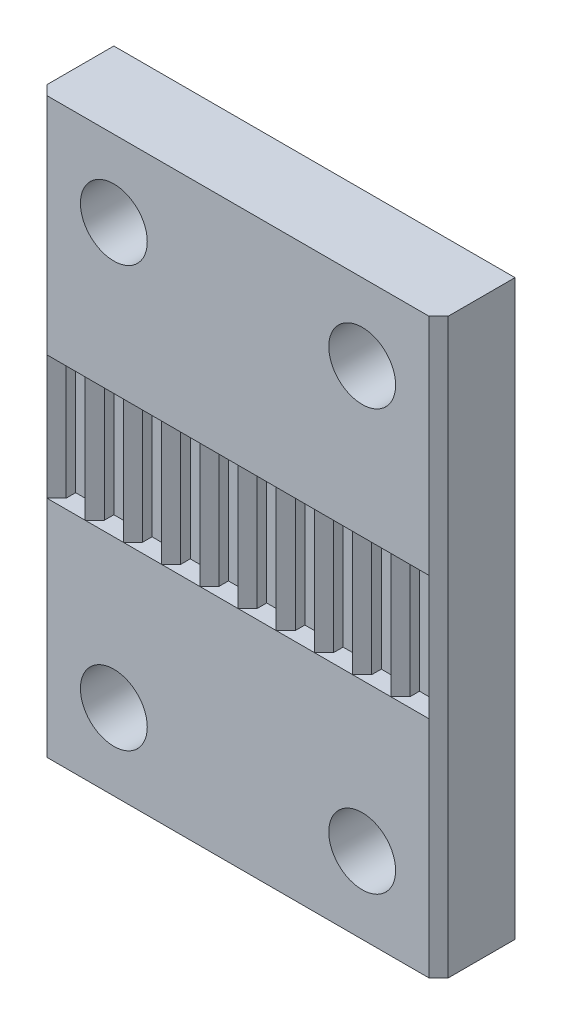
SolidWorks part; units mm, degrees
ref_plane "Front Plane" through (0, 0, 0) normal (0, 0, 1) x (1, 0, 0)
ref_plane "Top Plane" through (0, 0, 0) normal (0, 1, 0) x (1, 0, 0)
ref_plane "Right Plane" through (0, 0, 0) normal (1, 0, 0) x (0, 0, -1)
sketch "Sketch1" plane through (0, 0, 0) normal (0, 0, 1) x (1, 0, 0)
  line L0 (17, 24.25) -> (17, 26)
  line L1 (0, 0) -> (21, 0)
  line L2 (0, 0) -> (0, 30)
  line L3 (0, 30) -> (21, 30)
  line L4 (21, 0) -> (21, 30)
  line L5 (17, 4) -> (17, 5.75)
  line L7 (4, 4) -> (4, 5.75)
  line L8 (4, 24.25) -> (4, 26)
  line L10 (4, 4) -> (4, 26) construction
  line L11 (4, 4) -> (17, 4) construction
  line L12 (4, 26) -> (17, 26) construction
  line L13 (17, 4) -> (17, 26) construction
  circle A0 centre (4, 26) radius 1.75
  circle A1 centre (17, 26) radius 1.75
  circle A2 centre (17, 4) radius 1.75
  circle A3 centre (4, 4) radius 1.75
  dimension "D4" = 3.5
  dimension "D1" = 21
  dimension "D2" = 30
  dimension "D3" = 4
extrude "Boss-Extrude1" add sketch "Sketch1" along normal blind 4 contours L1 L4 L3 L2 A3 A2 A1 A0 region at (10.5, 15, 0)
sketch "Sketch2" plane through (0, 0, 4) normal (0, 0, 1) x (1, 0, 0)
  line L0 (10.5, 30) -> (10.5, 0) construction
  line L1 (0, 30) -> (21, 30) construction
  line L2 (0, 0) -> (21, 0) construction
  line L3 (21, 0) -> (21, 30) construction
  line L4 (0, 18.25) -> (21, 18.25)
  line L5 (0, 18.25) -> (0, 11.75)
  line L6 (0, 11.75) -> (21, 11.75)
  line L7 (21, 18.25) -> (21, 11.75)
  line L8 (0, 18.25) -> (21, 11.75) construction
  line L9 (0, 11.75) -> (21, 18.25) construction
  point P6 (10.5, 15)
  dimension "D1" = 6.5
extrude "Cut-Extrude1" cut sketch "Sketch2" against normal blind 1
sketch "Sketch3" plane through (0, 0, 3) normal (0, 0, 1) x (1, 0, 0)
  line L0 (0, 11.75) -> (21, 11.75) construction
  line L1 (0, 18.25) -> (1, 18.25)
  line L2 (0, 18.25) -> (0, 11.75)
  line L3 (0, 11.75) -> (1, 11.75)
  line L4 (1, 18.25) -> (1, 11.75)
  line L5 (2, 11.75) -> (3, 11.75)
  line L6 (3, 18.25) -> (3, 11.75)
  line L7 (2, 18.25) -> (2, 11.75)
  line L8 (2, 18.25) -> (3, 18.25)
  line L9 (4, 11.75) -> (5, 11.75)
  line L10 (5, 18.25) -> (5, 11.75)
  line L11 (4, 18.25) -> (4, 11.75)
  line L12 (4, 18.25) -> (5, 18.25)
  line L13 (6, 11.75) -> (7, 11.75)
  line L14 (7, 18.25) -> (7, 11.75)
  line L15 (6, 18.25) -> (6, 11.75)
  line L16 (6, 18.25) -> (7, 18.25)
  line L17 (8, 11.75) -> (9, 11.75)
  line L18 (9, 18.25) -> (9, 11.75)
  line L19 (8, 18.25) -> (8, 11.75)
  line L20 (8, 18.25) -> (9, 18.25)
  line L21 (10, 11.75) -> (11, 11.75)
  line L22 (11, 18.25) -> (11, 11.75)
  line L23 (10, 18.25) -> (10, 11.75)
  line L24 (10, 18.25) -> (11, 18.25)
  line L25 (12, 11.75) -> (13, 11.75)
  line L26 (13, 18.25) -> (13, 11.75)
  line L27 (12, 18.25) -> (12, 11.75)
  line L28 (12, 18.25) -> (13, 18.25)
  line L29 (14, 11.75) -> (15, 11.75)
  line L30 (15, 18.25) -> (15, 11.75)
  line L31 (14, 18.25) -> (14, 11.75)
  line L32 (14, 18.25) -> (15, 18.25)
  line L33 (16, 11.75) -> (17, 11.75)
  line L34 (17, 18.25) -> (17, 11.75)
  line L35 (16, 18.25) -> (16, 11.75)
  line L36 (16, 18.25) -> (17, 18.25)
  line L37 (18, 11.75) -> (19, 11.75)
  line L38 (19, 18.25) -> (19, 11.75)
  line L39 (18, 18.25) -> (18, 11.75)
  line L40 (18, 18.25) -> (19, 18.25)
  line L41 (20, 11.75) -> (21, 11.75)
  line L42 (21, 18.25) -> (21, 11.75)
  line L43 (20, 18.25) -> (20, 11.75)
  line L44 (20, 18.25) -> (21, 18.25)
  dimension "D1" = 1
  dimension "D2" = 11
extrude "Boss-Extrude2" add sketch "Sketch3" along normal blind 1
chamfer "Chamfer1" distance 0.5 angle 45 20 edges at (20, 15, 4) (19, 15, 4) (18, 15, 4) (17, 15, 4) (16, 15, 4) (15, 15, 4) (14, 15, 4) (13, 15, 4) (12, 15, 4) (11, 15, 4) (10, 15, 4) (9, 15, 4) (8, 15, 4) (7, 15, 4) (6, 15, 4) (5, 15, 4) (4, 15, 4) (3, 15, 4) (2, 15, 4) (1, 15, 4)
chamfer "Chamfer2" distance 0.5 angle 45 2 edges at (21, 15, 4) (0, 15, 4)
